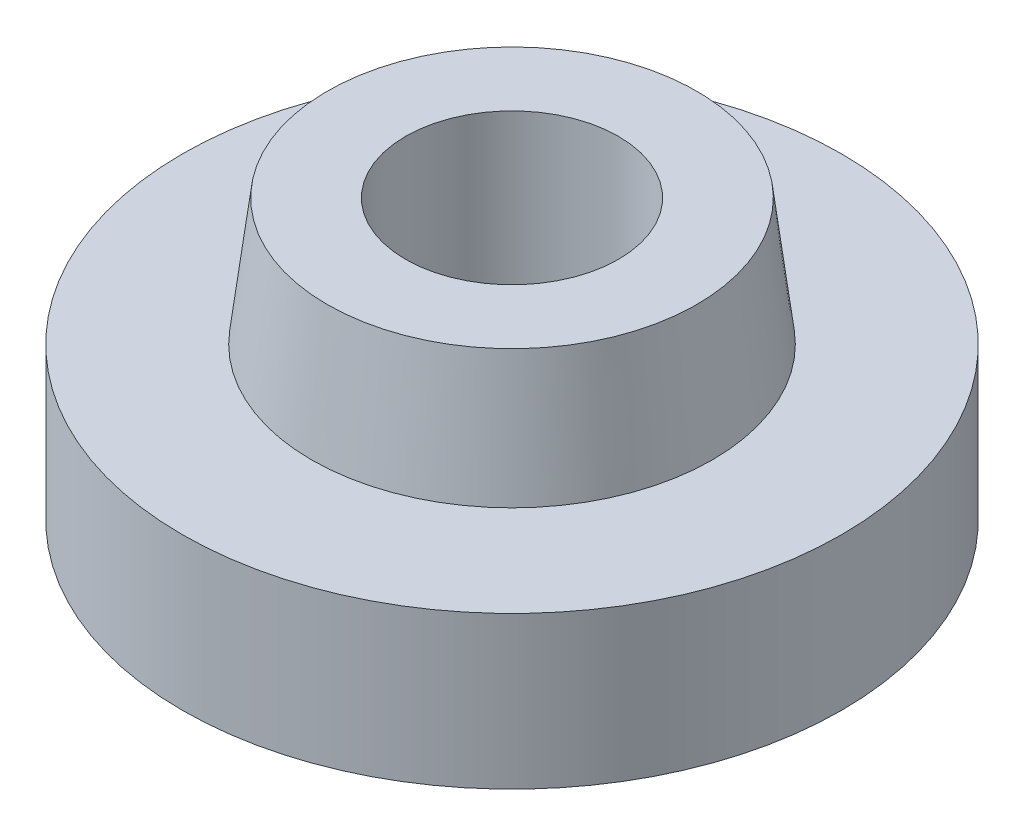
SolidWorks part; units mm, degrees
ref_plane "Front Plane" through (0, 0, 0) normal (0, 0, 1) x (1, 0, 0)
ref_plane "Top Plane" through (0, 0, 0) normal (0, 1, 0) x (1, 0, 0)
ref_plane "Right Plane" through (0, 0, 0) normal (1, 0, 0) x (0, 0, -1)
sketch "Sketch1" plane through (0, 0, 0) normal (0, 1, 0) x (1, 0, 0)
  circle A0 centre (0, 0) radius 2.1
  circle A1 centre (0, 0) radius 3.95
  dimension "D1" = 7.9
  dimension "D2" = 4.2
extrude "Boss-Extrude1" add sketch "Sketch1" along normal blind 2.5
sketch "Sketch2" plane through (0, 0, 0) normal (0, -1, 0) x (1, 0, 0)
  circle A0 centre (0, 0) radius 6.5
  circle A1 centre (0, 0) radius 2.1
  dimension "D1" = 13
extrude "Boss-Extrude2" add sketch "Sketch2" along normal blind 3
chamfer "Chamfer1" distance 2.5 angle 7 1 edges at (0, 2.5, 3.95) first distance on face at (0, 2.5, 3.95)
